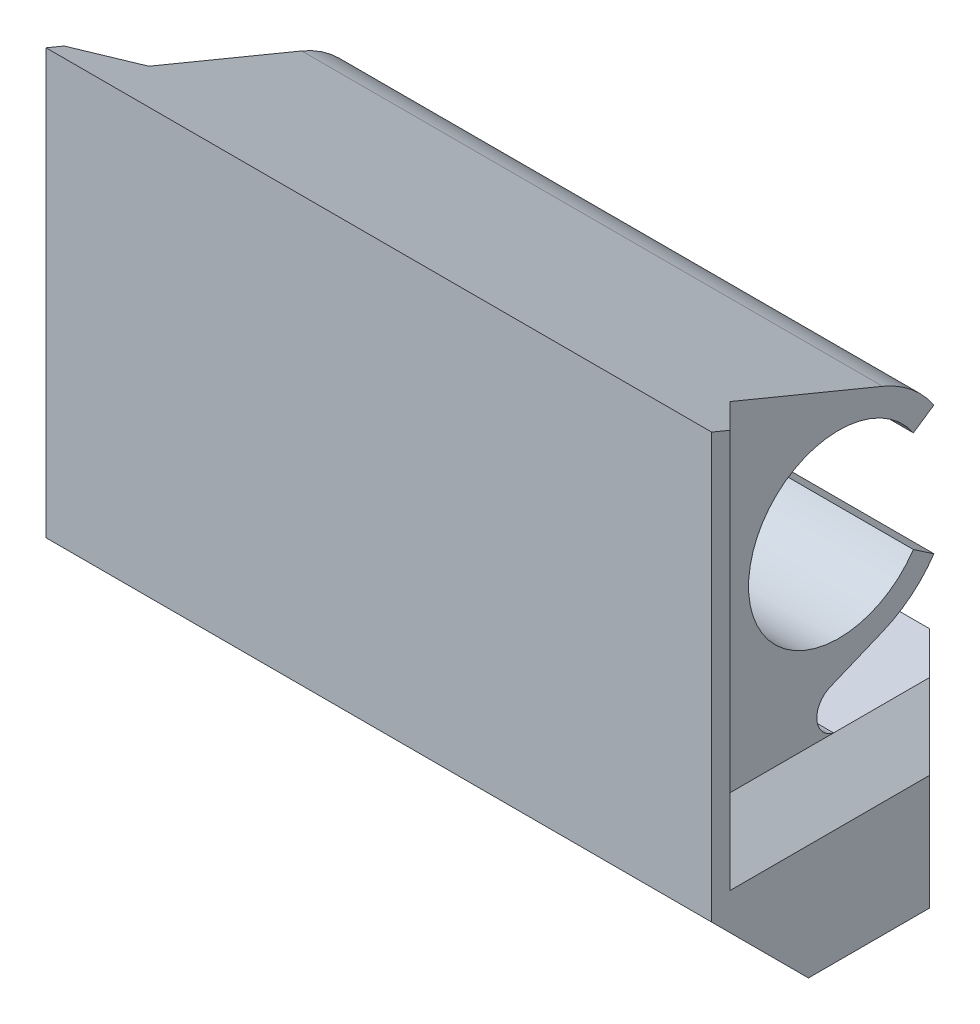
SolidWorks part; units mm, degrees
ref_plane "Front Plane" through (0, 0, 0) normal (0, 0, 1) x (1, 0, 0)
ref_plane "Top Plane" through (0, 0, 0) normal (0, 1, 0) x (1, 0, 0)
ref_plane "Right Plane" through (0, 0, 0) normal (1, 0, 0) x (0, 0, -1)
sketch "Sketch1" plane through (0, 0, 0) normal (0, 0, 1) x (1, 0, 0)
  line L1 (-10.3542, -6.2205) -> (44.6458, -6.2205)
  line L2 (-10.3542, -6.2205) -> (-10.3542, 38.7795)
  line L3 (-10.3542, 38.7795) -> (44.6458, 38.7795)
  line L4 (44.6458, -6.2205) -> (44.6458, 38.7795)
  dimension "D1" = 55
  dimension "D2" = 45
extrude "Boss-Extrude1" add sketch "Sketch1" along normal blind 5 contours L3 L4 L1 L2
sketch "Sketch3" plane through (0, 0, 0) normal (0, 0, -1) x (-1, 0, 0)
  line L0 (10.3542, -6.2205) -> (10.3542, 38.7795) construction
  line L1 (-44.6458, -6.2205) -> (10.3542, -6.2205)
  line L2 (-44.6458, -6.2205) -> (-44.6458, 6.7795)
  line L3 (-44.6458, 6.7795) -> (10.3542, 6.7795)
  line L4 (10.3542, -6.2205) -> (10.3542, 6.7795)
  dimension "D1" = 13
extrude "Boss-Extrude5" add sketch "Sketch3" along normal blind 20 contours L3 L4 L1 L2
chamfer "Chamfer1" distance 8 angle 45 1 edges at (17.1458, -6.2205, 5)
sketch "Sketch5" plane through (0, -6.2205, 0) normal (0, -1, 0) x (1, 0, 0)
  line L0 (44.6458, -20) -> (-10.3542, -20) construction
  line L1 (-10.3542, -3) -> (-10.3542, -20) construction
  circle A0 centre (-0.3542, -11) radius 4.5
  circle A1 centre (34.6458, -11) radius 4.5
  dimension "D1" = 35
  dimension "D2" = 9
  dimension "D3" = 10
extrude "Cut-Extrude2" cut sketch "Sketch5" against normal blind 8
sketch "Sketch6" plane through (-10.3542, 0, 0) normal (-1, 0, 0) x (0, 0, 1)
  line L0 (0, 6.7795) -> (0, 38.7795) construction
  line L1 (-20, 6.7795) -> (0, 6.7795) construction
  line L2 (-8.3082, 10.2139) -> (-12.6292, 12.0001)
  line L3 (-18.5, 20.7795) -> (-16.45, 20.7795) construction
  line L4 (0, 34.7795) -> (-12.6292, 29.559)
  line L5 (-16.1429, 18.6625) -> (-18.1084, 18.08)
  line L6 (-16.1429, 22.8965) -> (-18.1084, 23.479)
  line L7 (0, 34.7795) -> (0, 6.7795)
  line L8 (-1.55, 20.7795) -> (7.8073, 20.7795) construction
  line L10 (0, 6.7795) -> (-8.5765, 6.7795)
  arc A0 (-16.1429, 18.6625) -> (-16.1429, 22.8965) centre (-9, 20.7795) ccw
  arc A1 (-18.1084, 18.08) -> (-12.6292, 12.0001) centre (-9, 20.7795) ccw
  arc A2 (-12.6292, 29.559) -> (-18.1084, 23.479) centre (-9, 20.7795) ccw
  arc A3 (-8.5765, 6.7795) -> (-8.3082, 10.2139) centre (-9, 8.5403) ccw
  dimension "D1" = 9
  dimension "D2" = 14
ref_plane "Plane1" through (-6.8542, 0, 0) normal (-1, 0, 0) x (0, 0, 1)
sketch "Sketch7" plane through (-6.8542, 0, 0) normal (-1, 0, 0) x (0, 0, 1)
  line L1 (-20, 6.7795) -> (0, 6.7795) construction
  point P0 (0, 0)
  point P14 (0, 0)
  line B0 (-8.3082, 10.2139) -> (-12.6292, 12.0001)
  line B1 (-18.5, 20.7795) -> (-16.45, 20.7795) construction
  line B2 (0, 34.7795) -> (-12.6292, 29.559)
  line B3 (0, 34.7795) -> (0, 6.7795)
  line B4 (0, 6.7795) -> (-8.5765, 6.7795)
  arc B5 (-15.171, 16.6056) -> (-15.171, 24.9535) centre (-9, 20.7795) ccw
  arc B6 (-16.869, 15.4571) -> (-12.6292, 12.0001) centre (-9, 20.7795) ccw
  arc B7 (-12.6292, 29.559) -> (-16.869, 26.102) centre (-9, 20.7795) ccw
  arc B8 (-8.5765, 6.7795) -> (-8.3082, 10.2139) centre (-9, 8.5403) ccw
  line B9 (-15.171, 16.6056) -> (-16.869, 15.4571)
  line B10 (-15.171, 24.9535) -> (-16.869, 26.102)
sketch_block_instance "Block1-1"
sketch_block "Block1"
extrude "Boss-Extrude7" add sketch "Sketch7" against normal blind 48
sketch "Sketch8" plane through (-10.3542, 0, 0) normal (-1, 0, 0) x (0, 0, 1)
  line L0 (0, 34.7795) -> (5, 36.8464)
  line L1 (5, 1.7795) -> (5, 38.7795) construction
  line L2 (0, 34.7795) -> (-12.6292, 29.559) construction
  line L3 (5, 36.8464) -> (5, 38.7795)
  line L4 (5, 38.7795) -> (0, 38.7795)
  line L5 (0, 38.7795) -> (0, 34.7795)
extrude "Cut-Extrude3" cut sketch "Sketch8" against normal through all
chamfer "Chamfer2" distance 3.5 angle 45 2 edges at (-10.3542, 6.7795, -10) (-10.3542, 20.7795, 0)
chamfer "Chamfer3" distance 3.5 angle 45 2 edges at (44.6458, 20.7795, 0) (44.6458, 6.7795, -10)
chamfer "Chamfer4" distance 7 angle 45 2 edges at (44.6458, -1.4705, -20) (-10.3542, -1.4705, -20)
